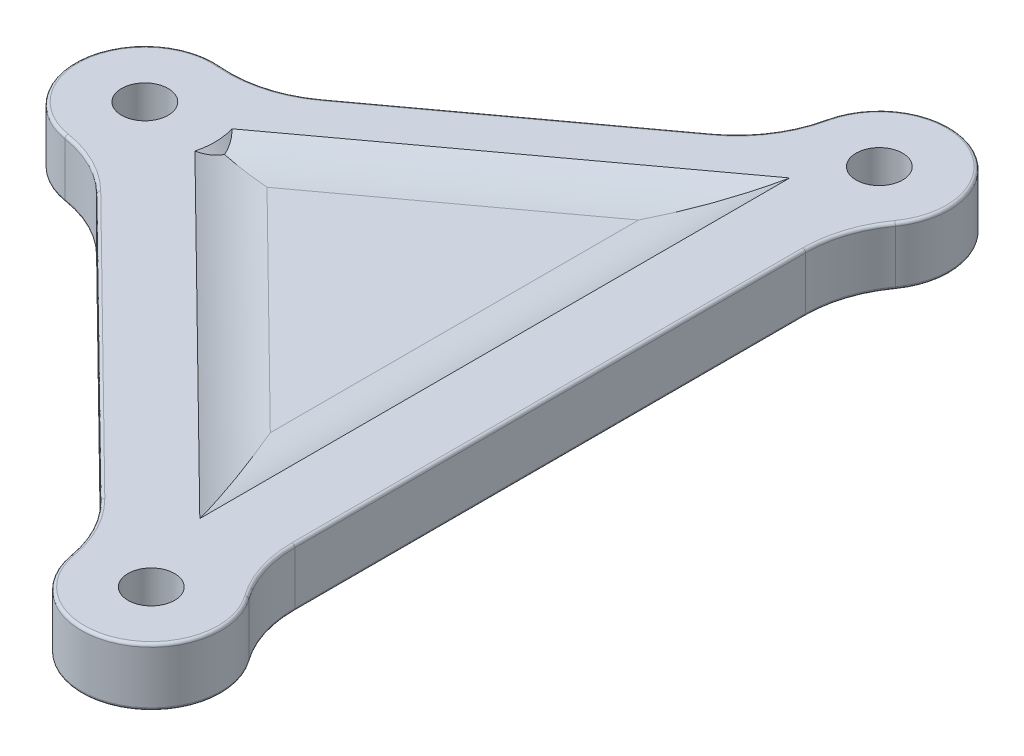
SolidWorks part; units mm, degrees
ref_plane "Front Plane" through (0, 0, 0) normal (0, 0, 1) x (1, 0, 0)
ref_plane "Top Plane" through (0, 0, 0) normal (0, 1, 0) x (1, 0, 0)
ref_plane "Right Plane" through (0, 0, 0) normal (1, 0, 0) x (0, 0, -1)
sketch "Sketch4" plane through (0, 0, 0) normal (0, 1, 0) x (1, 0, 0)
  line L0 (3, 0) -> (-3, 0) construction
  line L1 (3, 0) -> (3, 62.5) construction
  line L2 (-3, 0) -> (-3, 62.5) construction
  line L3 (3, 62.5) -> (-3, 62.5) construction
  line L4 (-2.1049, -2.1376) -> (-38.4436, 33.6465) construction
  line L5 (-2.1049, -2.1376) -> (2.1049, 2.1376)
  line L6 (-38.4436, 33.6465) -> (-34.2338, 37.9216)
  line L7 (2.1049, 2.1376) -> (-34.2338, 37.9216) construction
  line L8 (-37.5234, 37.3954) -> (-1.1847, 64.1114) construction
  line L9 (-37.5234, 37.3954) -> (-35.154, 34.1727) construction
  line L10 (-1.1847, 64.1114) -> (1.1847, 60.8886)
  line L11 (-35.154, 34.1727) -> (1.1847, 60.8886) construction
  circle A0 centre (0, 0) radius 6 construction
  circle A1 centre (0, 0) radius 2 construction
  circle A2 centre (0, 62.5) radius 6 construction
  circle A3 centre (0, 62.5) radius 2 construction
  circle A4 centre (-36.3387, 35.7841) radius 6 construction
  circle A5 centre (-36.3387, 35.7841) radius 2 construction
  dimension "D1" = 12
  dimension "D2" = 4
  dimension "D3" = 62.5
  dimension "D4" = 6
  dimension "D5" = 6
  dimension "D6" = 45.441
  dimension "D7" = 51
sketch "Sketch5" plane through (0, 0, 0) normal (0, 1, 0) x (1, 0, 0)
  line L0 (-37.5234, 37.3954) -> (-1.1847, 64.1114) construction
  line L1 (-2.1049, -2.1376) -> (-38.4436, 33.6465) construction
  line L2 (3, 0) -> (3, 62.5) construction
  line L3 (-32.9657, 40.7462) -> (-5.7423, 60.7606)
  line L4 (-5.8073, 1.5083) -> (-34.7413, 30.0006)
  line L5 (3, 5.1962) -> (3, 57.3038)
  circle A0 centre (-36.3387, 35.7841) radius 6 construction
  circle A1 centre (0, 0) radius 6 construction
  circle A2 centre (0, 62.5) radius 6 construction
  arc A3 (-32.9657, 40.7462) -> (-34.7413, 30.0006) centre (-36.3387, 35.7841) ccw
  arc A4 (-5.8073, 1.5083) -> (3, 5.1962) centre (0, 0) ccw
  arc A5 (3, 57.3038) -> (-5.7423, 60.7606) centre (0, 62.5) ccw
extrude "Boss-Extrude1" add sketch "Sketch5" along normal mid plane 5
sketch "Sketch6" plane through (0, 2.5, 0) normal (0, 1, 0) x (1, 0, 0)
  circle A0 centre (-36.3387, 35.7841) radius 2 construction
  circle A1 centre (0, 62.5) radius 2 construction
  circle A2 centre (0, 0) radius 2 construction
  circle A3 centre (-36.3387, 35.7841) radius 2
  circle A4 centre (0, 62.5) radius 2
  circle A5 centre (0, 0) radius 2
extrude "Cut-Extrude2" cut sketch "Sketch6" against normal through all
sketch "Sketch7" [suppressed] plane through (0, 5, 0) normal (0, 1, 0) x (1, 0, 0)
  circle A0 centre (0, 0) radius 6 construction
  circle A1 centre (0, 0) radius 6
sketch "Sketch8" [suppressed] plane through (0, 0, 0) normal (0, -1, 0) x (1, 0, 0)
  circle A0 centre (0, 0) radius 6 construction
  circle A1 centre (0, 0) radius 6
fillet "Fillet1" radius 10 6 edges at (-5.8073, 0, -1.5083) (-34.7413, 0, -30.0006) (-32.9657, 0, -40.7462) (-5.7423, 0, -60.7606) (3, 0, -57.3038) (3, 0, -5.1962)
fillet "Fillet2" radius 0.25 24 edges at (-34.3163, 2.5, -28.9081) (-42.2941, 2.5, -36.5146) (-32.2279, 2.5, -42.0903) (-19.354, 2.5, -50.7534) (-7.2453, 2.5, -60.4573) (2.4369, 2.5, -67.9828) (3.4803, 2.5, -56.2345) (3, 2.5, -31.25) (3.4803, 2.5, -6.2655) (2.3174, 2.5, 5.5344) (-6.9063, 2.5, -1.9164) (-34.3163, -2.5, -28.9081) (-42.2941, -2.5, -36.5146) (-32.2279, -2.5, -42.0903) (-19.354, -2.5, -50.7534) (-7.2453, -2.5, -60.4573) (2.4369, -2.5, -67.9828) (3.4803, -2.5, -56.2345) (3, -2.5, -31.25) (3.4803, -2.5, -6.2655) (2.3174, -2.5, 5.5344) (-6.9063, -2.5, -1.9164) (-20.2743, 2.5, -15.7545) (-20.2743, -2.5, -15.7545)
sketch "Sketch11" plane through (0, 2.5, 0) normal (0, 1, 0) x (1, 0, 0)
  line L0 (-35.154, 34.1727) -> (1.1847, 60.8886) construction
  line L1 (2.1049, 2.1376) -> (-34.2338, 37.9216) construction
  line L2 (-3, 0) -> (-3, 62.5) construction
  line L3 (-30.5964, 37.5234) -> (-3, 57.8121)
  line L4 (-3, 7.1646) -> (-30.5314, 34.2758)
  line L5 (-3, 7.1646) -> (-3, 57.8121)
  circle A0 centre (-36.3387, 35.7841) radius 6 construction
  arc A1 (-30.5314, 34.2758) -> (-30.5964, 37.5234) centre (-36.3387, 35.7841) ccw
extrude "Cut-Extrude3" cut sketch "Sketch11" against normal blind 1 draft 45
fillet "Fillet3" radius 10 3 edges at (-16.7195, 1.5, -22.0781) (-16.733, 1.5, -46.4745) (-4, 1.5, -32.6943)
mirror "Mirror1" about plane through (0, 0, 0) normal (0, 1, 0) of "Fillet3", "Cut-Extrude3"
